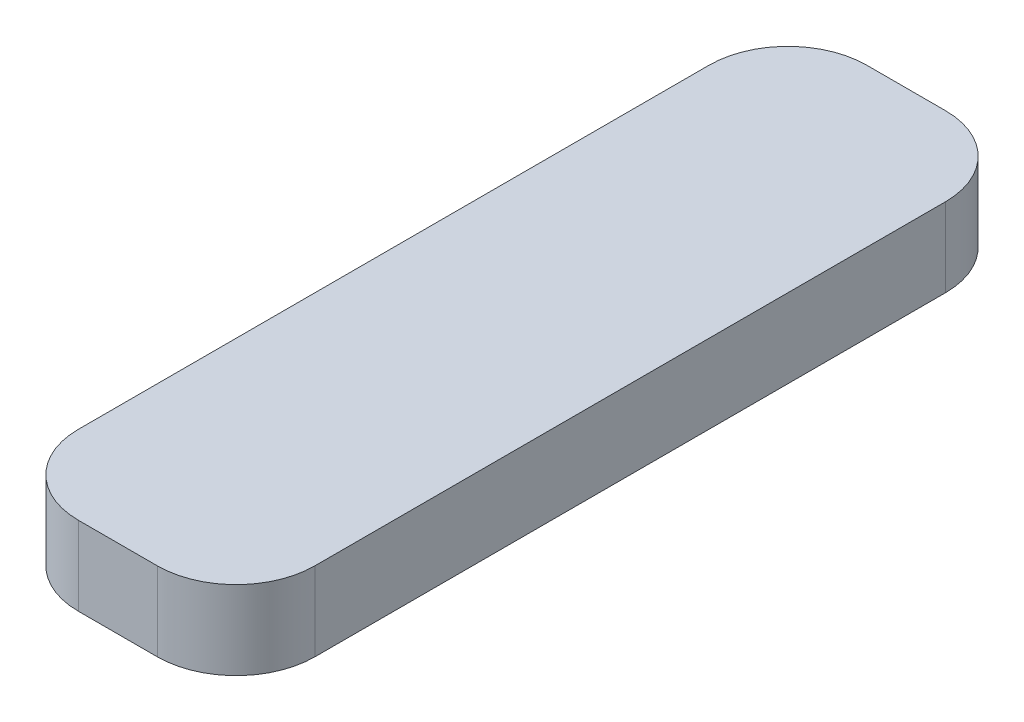
SolidWorks part; units mm, degrees
ref_plane "Front Plane" through (0, 0, 0) normal (0, 0, 1) x (1, 0, 0)
ref_plane "Top Plane" through (0, 0, 0) normal (0, 1, 0) x (1, 0, 0)
ref_plane "Right Plane" through (0, 0, 0) normal (1, 0, 0) x (0, 0, -1)
sketch "Sketch1" plane through (0, 0, 0) normal (0, 1, 0) x (1, 0, 0)
  line L1 (0, 0) -> (30, 0)
  line L2 (0, 0) -> (0, 100)
  line L3 (0, 100) -> (30, 100)
  line L4 (30, 0) -> (30, 100)
  dimension "D1" = 100
  dimension "D2" = 30
extrude "Boss-Extrude1" add sketch "Sketch1" along normal blind 10
ref_plane "Plane1" through (15, 0, 0) normal (-1, 0, 0) x (0, 0, 1)
fillet "Fillet1" radius 10 4 edges at (30, 5, -100) (30, 5, 0) (0, 5, 0) (0, 5, -100)
